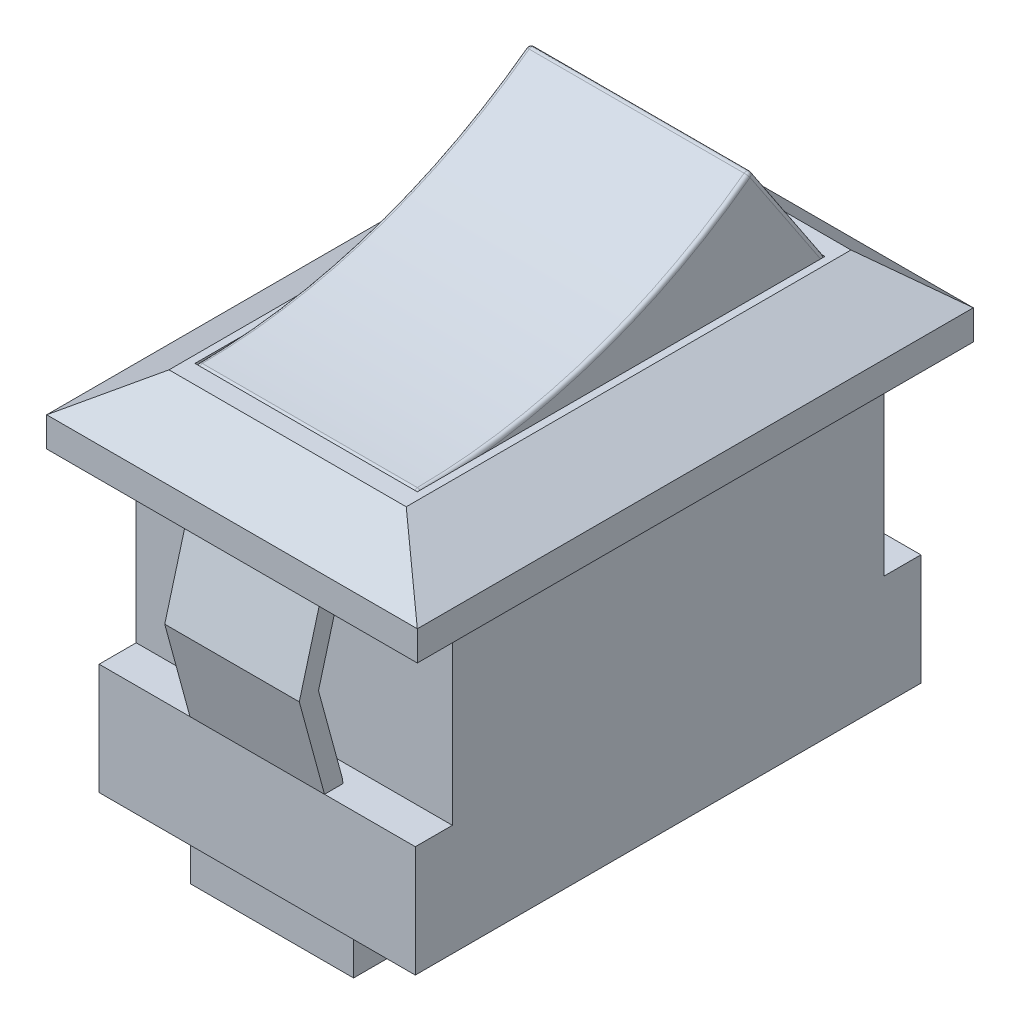
SolidWorks part; units mm, degrees
ref_plane "Front Plane" through (0, 0, 0) normal (0, 0, 1) x (1, 0, 0)
ref_plane "Top Plane" through (0, 0, 0) normal (0, 1, 0) x (1, 0, 0)
ref_plane "Right Plane" through (0, 0, 0) normal (1, 0, 0) x (0, 0, -1)
sketch "Sketch1" plane through (0, 0, 0) normal (0, 1, 0) x (1, 0, 0)
  line L1 (4.265, -6.82) -> (-4.265, -6.82)
  line L2 (4.265, -6.82) -> (4.265, 6.82)
  line L3 (4.265, 6.82) -> (-4.265, 6.82)
  line L4 (-4.265, -6.82) -> (-4.265, 6.82)
  line L5 (4.265, -6.82) -> (-4.265, 6.82) construction
  line L6 (4.265, 6.82) -> (-4.265, -6.82) construction
  point P0 (0, 0)
  dimension "D1" = 13.64
  dimension "D2" = 8.53
extrude "Boss-Extrude1" add sketch "Sketch1" along normal blind 10
sketch "Sketch2" plane through (-4.265, 0, 0) normal (-1, 0, 0) x (0, 0, 1)
  line L0 (-6.82, 10) -> (-6.82, 0) construction
  line L1 (-6.82, 3) -> (-5.82, 3)
  line L2 (-6.82, 3) -> (-6.82, 8)
  line L3 (-6.82, 8) -> (-5.82, 8)
  line L4 (-5.82, 3) -> (-5.82, 8)
  line L5 (6.82, 10) -> (6.82, 0) construction
  line L6 (6.82, 8) -> (5.82, 8)
  line L7 (6.82, 8) -> (6.82, 3)
  line L8 (6.82, 3) -> (5.82, 3)
  line L9 (5.82, 8) -> (5.82, 3)
  line L10 (-6.82, 0) -> (6.82, 0) construction
  line L11 (-6.82, 10) -> (6.82, 10) construction
  dimension "D1" = 1
  dimension "D2" = 1
  dimension "D3" = 3
  dimension "D4" = 3
  dimension "D5" = 2
extrude "Cut-Extrude1" cut sketch "Sketch2" against normal through all
sketch "Sketch3" plane through (0, 10, 0) normal (0, 1, 0) x (1, 0, 0)
  line L1 (3, -5.5) -> (-3, -5.5)
  line L2 (3, -5.5) -> (3, 5.5)
  line L3 (3, 5.5) -> (-3, 5.5)
  line L4 (-3, -5.5) -> (-3, 5.5)
  line L5 (3, -5.5) -> (-3, 5.5) construction
  line L6 (3, 5.5) -> (-3, -5.5) construction
  point P0 (0, 0)
  dimension "D1" = 11
  dimension "D2" = 6
extrude "Cut-Extrude2" cut sketch "Sketch3" against normal blind 0.5
sketch "Sketch4" plane through (0, 10, 0) normal (0, 1, 0) x (1, 0, 0)
  line L1 (5, -7.5) -> (-5, -7.5)
  line L2 (5, -7.5) -> (5, 7.5)
  line L3 (5, 7.5) -> (-5, 7.5)
  line L4 (-5, -7.5) -> (-5, 7.5)
  line L5 (5, -7.5) -> (-5, 7.5) construction
  line L6 (5, 7.5) -> (-5, -7.5) construction
  point P0 (0, 0)
  line M5 (-3, -5.5) -> (-3, 5.5)
  line M6 (-3, 5.5) -> (3, 5.5)
  line M7 (3, 5.5) -> (3, -5.5)
  line M8 (3, -5.5) -> (-3, -5.5)
  line M9 (-4.265, 6.82) -> (-4.265, -6.82)
  line M10 (-4.265, -6.82) -> (4.265, -6.82)
  line M11 (4.265, -6.82) -> (4.265, 6.82)
  line M12 (4.265, 6.82) -> (-4.265, 6.82)
  dimension "D1" = 10
  dimension "D2" = 15
extrude "Boss-Extrude2" add sketch "Sketch4" against normal up to vertex (2 mm away) contours L4 L1 L2 L3 M9 M12 M11 M10 | M12 M9 M10 M11 M8 M5 M6 M7 region at (0, 10, 7.3197) region at (0, 10, -6.6591) up to point (4.265, 8, 6.82)
sketch "Sketch5" plane through (0, 10, 0) normal (0, 1, 0) x (1, 0, 0)
  line L8 (-3.5, 6) -> (-3.5, -6)
  line L9 (-3.5, -6) -> (3.5, -6)
  line L10 (3.5, -6) -> (3.5, 6)
  line L11 (3.5, 6) -> (-3.5, 6)
  line L12 (-3.5, 6) -> (-3.5, -6) construction
  line L13 (-3.5, -6) -> (3.5, -6) construction
  line L14 (3.5, -6) -> (3.5, 6) construction
  line L15 (3.5, 6) -> (-3.5, 6) construction
  dimension "D1" = 0.5
chamfer "Chamfer1" distance 1.5 distance2 1.2 1 edges at (0, 10, 7.5) first distance on face at (0, 10, 0)
chamfer "Chamfer2" distance 1.2 distance2 1.5 1 edges at (0, 10, -7.5) first distance on face at (0, 9, -7.5)
chamfer "Chamfer3" distance 1.8 distance2 1.2 1 edges at (-5, 10, 0) first distance on face at (0, 10, 0)
chamfer "Chamfer4" distance 1.2 distance2 1.8 1 edges at (5, 10, 0) first distance on face at (5, 8.9333, 0)
sketch "Sketch6" plane through (0, 0, 0) normal (1, 0, 0) x (0, 0, -1)
  line L0 (-6.82, 8) -> (-7.5, 5.5)
  line L1 (-7.5, 8) -> (7.5, 8) construction
  line L2 (-7.5, 5.5) -> (-6.82, 3)
  line L3 (-5.82, 8) -> (-5.82, 3) construction
  line L4 (6.32, 3) -> (6.82, 3)
  line L9 (-6.3375, 7.8688) -> (-6.9818, 5.5)
  line L10 (-6.9818, 5.5) -> (-6.3375, 3.1312)
  line L11 (-6.82, 8) -> (-6.3375, 8)
  line L12 (-6.3375, 8) -> (-6.3375, 7.8688)
  line L13 (-6.3375, 3.1312) -> (-6.32, 3)
  line L14 (-5.82, 3) -> (-6.82, 3) construction
  line L15 (-6.32, 3) -> (-6.82, 3)
  line L16 (0, 0) -> (0, 8) construction
  line L17 (-6.82, 0) -> (6.82, 0) construction
  line L18 (6.3375, 3.1312) -> (6.32, 3)
  line L19 (6.3375, 8) -> (6.3375, 7.8688)
  line L20 (6.82, 8) -> (6.3375, 8)
  line L21 (6.9818, 5.5) -> (6.3375, 3.1312)
  line L22 (6.3375, 7.8688) -> (6.9818, 5.5)
  line L23 (7.5, 5.5) -> (6.82, 3)
  line L24 (6.82, 8) -> (7.5, 5.5)
  point P9 (-5.82, 5.5)
  dimension "D1" = 0.5
extrude "Boss-Extrude3" add sketch "Sketch6" along normal mid plane 3.63
sketch "Sketch7" plane through (0, 0, 0) normal (0, -1, 0) x (1, 0, 0)
  line L0 (-4.265, 6.82) -> (4.265, 6.82) construction
  line L1 (3.5, 1.25) -> (-3.5, 1.25)
  line L2 (3.5, 1.25) -> (3.5, -1.25)
  line L3 (3.5, -1.25) -> (-3.5, -1.25)
  line L4 (-3.5, 1.25) -> (-3.5, -1.25)
  line L5 (3.5, 1.25) -> (-3.5, -1.25) construction
  line L6 (3.5, -1.25) -> (-3.5, 1.25) construction
  line L7 (-3.5, -6.42) -> (3.5, -6.42)
  line L8 (-3.5, -6.42) -> (-3.5, -3.92)
  line L9 (-3.5, -3.92) -> (3.5, -3.92)
  line L10 (3.5, -6.42) -> (3.5, -3.92)
  line L11 (-3.5, 3.92) -> (3.5, 3.92)
  line L12 (-3.5, 3.92) -> (-3.5, 6.42)
  line L13 (-3.5, 6.42) -> (3.5, 6.42)
  line L14 (3.5, 3.92) -> (3.5, 6.42)
  point P0 (0, 0)
  dimension "D1" = 2.5
  dimension "D2" = 7
  dimension "D3" = 0.4
  dimension "D4" = 0.4
  dimension "D5" = 2.5
  dimension "D6" = 2.5
extrude "Boss-Extrude4" add sketch "Sketch7" along normal blind 0.3
sketch "Sketch8" plane through (0, -0.3, 0) normal (0, -1, 0) x (1, 0, 0)
  line L0 (3.5, 1.25) -> (-3.5, 1.25) construction
  line L1 (2.2, -1.25) -> (-2.2, -1.25)
  line L2 (2.2, -1.25) -> (2.2, 1.25)
  line L3 (2.2, 1.25) -> (-2.2, 1.25)
  line L4 (-2.2, -1.25) -> (-2.2, 1.25)
  line L5 (2.2, -1.25) -> (-2.2, 1.25) construction
  line L6 (2.2, 1.25) -> (-2.2, -1.25) construction
  line L7 (3.5, 6.42) -> (-3.5, 6.42) construction
  line L8 (2.2, 3.92) -> (-2.2, 3.92)
  line L9 (2.2, 3.92) -> (2.2, 6.42)
  line L10 (2.2, 6.42) -> (-2.2, 6.42)
  line L11 (-2.2, 3.92) -> (-2.2, 6.42)
  line L12 (2.2, 3.92) -> (-2.2, 6.42) construction
  line L13 (2.2, 6.42) -> (-2.2, 3.92) construction
  line L14 (3.5, -3.92) -> (-3.5, -3.92) construction
  line L15 (2.2, -6.42) -> (-2.2, -6.42)
  line L16 (2.2, -6.42) -> (2.2, -3.92)
  line L17 (2.2, -3.92) -> (-2.2, -3.92)
  line L18 (-2.2, -6.42) -> (-2.2, -3.92)
  line L19 (2.2, -6.42) -> (-2.2, -3.92) construction
  line L20 (2.2, -3.92) -> (-2.2, -6.42) construction
  line L21 (-3.5, -6.42) -> (3.5, -6.42) construction
  line L22 (2.5, -0.2) -> (-2.5, -0.2)
  line L23 (2.5, -0.2) -> (2.5, 0.2)
  line L24 (2.5, 0.2) -> (-2.5, 0.2)
  line L25 (-2.5, -0.2) -> (-2.5, 0.2)
  line L26 (2.5, -0.2) -> (-2.5, 0.2) construction
  line L27 (2.5, 0.2) -> (-2.5, -0.2) construction
  line L28 (2.5, -5.37) -> (-2.5, -5.37)
  line L29 (2.5, -5.37) -> (2.5, -4.97)
  line L30 (2.5, -4.97) -> (-2.5, -4.97)
  line L31 (-2.5, -5.37) -> (-2.5, -4.97)
  line L32 (2.5, -5.37) -> (-2.5, -4.97) construction
  line L33 (2.5, -4.97) -> (-2.5, -5.37) construction
  line L34 (2.5, 4.97) -> (-2.5, 4.97)
  line L35 (2.5, 4.97) -> (2.5, 5.37)
  line L36 (2.5, 5.37) -> (-2.5, 5.37)
  line L37 (-2.5, 4.97) -> (-2.5, 5.37)
  line L38 (2.5, 4.97) -> (-2.5, 5.37) construction
  line L39 (2.5, 5.37) -> (-2.5, 4.97) construction
  line L40 (-3.5, 3.92) -> (3.5, 3.92) construction
  line L41 (1.7, 4.42) -> (1.7, 5.92)
  line L46 (1.1867, 4.1897) -> (-1.1867, 6.1503) construction
  line L47 (1.1867, 6.1503) -> (-1.1867, 4.1897) construction
  line L48 (1.7, 5.92) -> (-1.7, 5.92)
  line L49 (-1.7, 4.42) -> (-1.7, 5.92)
  line L50 (1.7, 4.42) -> (-1.7, 4.42)
  line L51 (1.7, -0.75) -> (1.7, 0.75)
  line L52 (1.7, 0.75) -> (-1.7, 0.75)
  line L53 (-1.7, -0.75) -> (-1.7, 0.75)
  line L54 (1.7, -0.75) -> (-1.7, -0.75)
  line L55 (1.7, -5.92) -> (1.7, -4.42)
  line L56 (1.7, -4.42) -> (-1.7, -4.42)
  line L57 (-1.7, -5.92) -> (-1.7, -4.42)
  line L58 (1.7, -5.92) -> (-1.7, -5.92)
  point P0 (0, 0)
  point P8 (0, 5.17)
  point P15 (0, -5.17)
  point P22 (0, 0)
  point P27 (0, -5.17)
  point P32 (0, 5.17)
  point P42 (0, 5.17)
  line M10 (-3.5, -6.42) -> (3.5, -6.42)
  line M12 (3.5, -3.92) -> (-3.5, -3.92)
  dimension "D1" = 0.4
  dimension "D2" = 0.4
  dimension "D3" = 4.4
  dimension "D4" = 4.4
  dimension "D5" = 4.4
  dimension "D6" = 5
  dimension "D7" = 0.5
  dimension "D8" = 0.5
  dimension "D9" = 0.5
extrude "Boss-Extrude5" add sketch "Sketch8" along normal blind 1 contours L36 L49 L48 L41 L9 L10 L11 | L41 L50 L49 L34 L11 L8 L9 | L24 L53 L52 L51 L2 L3 L4 | L51 L54 L53 L22 L4 L1 L2 | L30 L57 L56 L55 L16 L18 M12 | L55 L58 L57 L28 L18 L16 M10 region at (0, -0.3, -0.895) region at (0, -0.3, 0.895) region at (0, -0.3, 4.275) region at (0, -0.3, 6.065) region at (0, -0.3, -6.065) region at (0, -0.3, -4.275)
extrude "Cut-Extrude4" cut sketch "Sketch8<5>" against normal blind 1 contours L31 L30 L29 L28 | L41 L48 L49 L50 | L35 L34 L37 L36 | L51 L52 L53 L54 | L23 L22 L25 L24 | L55 L56 L57 L58
sketch "Sketch8<5>" plane through (0, -0.3, 0) normal (0, -1, 0) x (1, 0, 0) same geometry as "Sketch8"
sketch "Sketch10" plane through (0, 0, 0) normal (0, 0, 1) x (1, 0, 0)
  line L0 (-4.265, 0) -> (4.265, 0) construction
  line L1 (1.85, 0) -> (-1.85, 0)
  line L3 (1.35, -7) -> (-1.35, -7)
  line L4 (-1.85, -1.3) -> (-1.85, -6.5)
  line L5 (1.85, -6.5) -> (1.35, -7)
  line L10 (3.5, 0) -> (-3.5, 0) construction
  line L11 (2.5, -0.3) -> (2.2, -0.3)
  line L12 (2.5, -0.3) -> (2.5, 0)
  line L13 (2.5, 0) -> (-2.5, 0)
  line L14 (-2.5, -0.3) -> (-2.5, 0)
  line L15 (2.2, -1.3) -> (2.2, -0.3) construction
  line L17 (2.2, -0.3) -> (2.2, -1.3)
  line L18 (2.2, -1.3) -> (-2.2, -1.3)
  line L19 (-2.2, -0.3) -> (-2.2, -1.3)
  line L20 (2.2, -1.3) -> (1.85, -1.65)
  line L21 (-2.2, -1.3) -> (-1.85, -1.65)
  line L22 (1.85, -1.3) -> (1.85, -6.5)
  line L23 (-2.2, -0.3) -> (-2.5, -0.3)
  line L24 (0, -5.5) -> (0, -3.7) construction
  line L25 (-0.5, -5.5) -> (-0.5, -3.7)
  line L26 (0.5, -5.5) -> (0.5, -3.7)
  line L27 (-1.35, -7) -> (-1.85, -6.5)
  arc A0 (-0.5, -5.5) -> (0.5, -5.5) centre (0, -5.5) ccw
  arc A1 (0.5, -3.7) -> (-0.5, -3.7) centre (0, -3.7) ccw
  point P1 (-1.85, -7)
  point P2 (1.85, -7)
  point P6 (0, 0)
  point P30 (0, -4.6)
  point P35 (0, -6)
  dimension "D6" = 0.5
  dimension "D1" = 7
  dimension "D2" = 3.7
  dimension "D3" = 45
  dimension "D4" = 45
  dimension "D5" = 1.8
  dimension "D7" = 1
extrude "Boss-Extrude6" add sketch "Sketch10" along normal mid plane 0.3 contours L27 L3 L5 L22 L18 L4 A1 L26 A0 L25 | L23 L19 L18 L17 L11 L12 L13 L1 L14 region at (0, -0.6347, 0) region at (1.782, -1.475, 0)
pattern_linear "LPattern1" count 2 spacing 5.1725 along (0, 0, -1) of "Boss-Extrude6"
sketch "Sketch11" plane through (0, 0, 0) normal (1, 0, 0) x (0, 0, -1)
  line L0 (5.5, 9.5) -> (-5.5, 9.5)
  line L1 (-5.5, 9.5) -> (5.5, 9.5) construction
  line L2 (-5.5, 9.5) -> (-5.5, 9.9003)
  line L3 (-5.5, 10) -> (5.5, 10) construction
  line L4 (5.5, 9.9697) -> (5.5, 9.5)
  line L5 (5.4832, 10.0252) -> (3.5584, 12.9124)
  line L6 (-5.5, 25) -> (-5.5, 10) construction
  line L7 (-5.5, 25) -> (5.1066, 14.3934) construction
  circle A0 centre (-5.5, 25) radius 15 construction
  arc A1 (3.4158, 12.9373) -> (-5.4007, 10.0003) centre (-5.5, 25) cw
  arc A2 (5.4832, 10.0252) -> (5.5, 9.9697) centre (5.4, 9.9697) cw
  arc A3 (3.5584, 12.9124) -> (3.4158, 12.9373) centre (3.4752, 12.8569) ccw
  arc A4 (-5.5, 9.9003) -> (-5.4007, 10.0003) centre (-5.4, 9.9003) cw
  point P19 (3.5, 13)
  dimension "D3" = 45
  dimension "D4" = 0.1
  dimension "D1" = 3
  dimension "D2" = 2
extrude "Boss-Extrude7" add sketch "Sketch11" along normal mid plane 6 separate body
fillet "Fillet1" radius 0.1 14 edges at (-3, 9.7349, -5.5) (-3, 9.9987, -5.4957) (-3, 11.4688, -4.5208) (-3, 12.9554, -3.4925) (-3, 9.7002, 5.5) (-3, 9.9708, 5.4709) (3, 9.7349, -5.5) (3, 9.9987, -5.4957) (3, 11.4688, -4.5208) (3, 12.9554, -3.4925) (3, 9.7002, 5.5) (3, 9.9708, 5.4709) (-3, 10.7689, 0.7593) (3, 10.7689, 0.7593)
sketch "Sketch12" plane through (0, 0, -5.3225) normal (0, 0, -1) x (-1, 0, 0)
  line L1 (-5.5074, -2) -> (6.719, -2)
  line L2 (-5.5074, -2) -> (-5.5074, -8.1132)
  line L3 (-5.5074, -8.1132) -> (6.719, -8.1132)
  line L4 (6.719, -2) -> (6.719, -8.1132)
  dimension "D1" = 6.1132
  dimension "D2" = 12.2265
  dimension "D3" = 2
  dimension "D4" = 6.719
extrude "Cut-Extrude5" cut sketch "Sketch12" against normal through all
